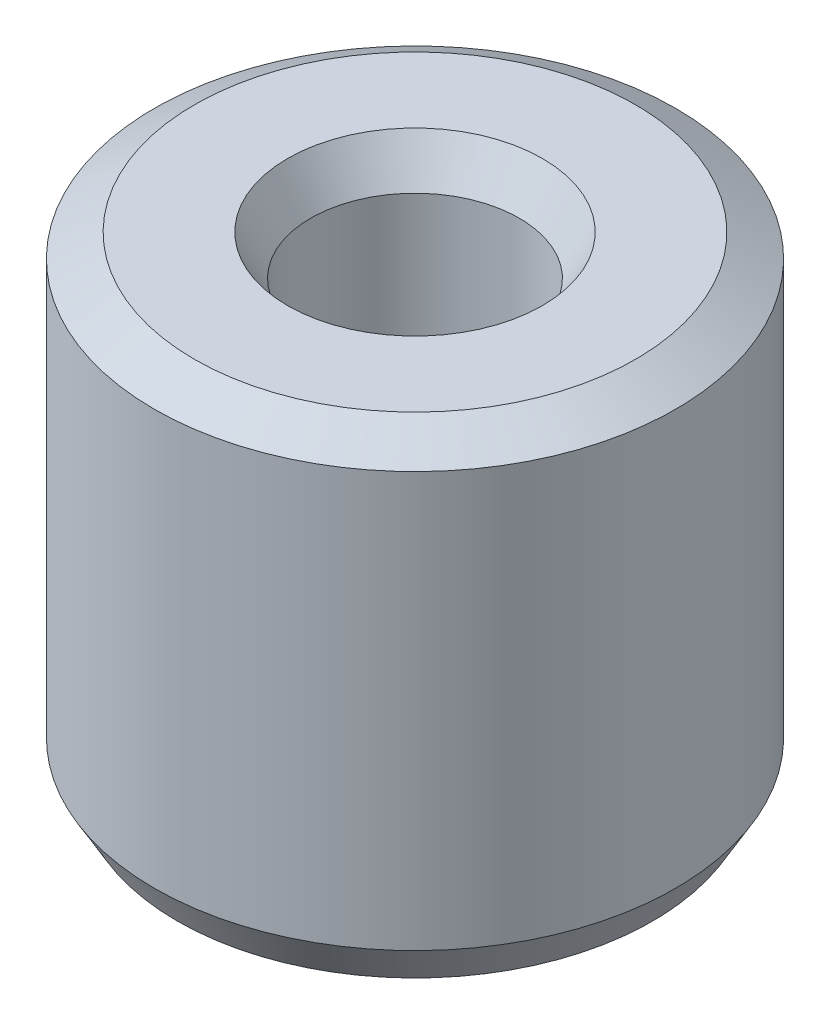
SolidWorks part; units mm, degrees
ref_plane "Front Plane" through (0, 0, 0) normal (0, 0, 1) x (1, 0, 0)
ref_plane "Top Plane" through (0, 0, 0) normal (0, 1, 0) x (1, 0, 0)
ref_plane "Right Plane" through (0, 0, 0) normal (1, 0, 0) x (0, 0, -1)
sketch "Sketch1" plane through (0, 0, 0) normal (0, 1, 0) x (1, 0, 0)
  circle A0 centre (0, 0) radius 32.5
  dimension "SLEEVE_OD" = 65
extrude "Boss-Extrude1" add sketch "Sketch1" along normal blind 59.6158
sketch "Sketch2" plane through (0, 0, 0) normal (0, 1, 0) x (1, 0, 0)
  circle A0 centre (0, 0) radius 13.0048
  dimension "BORE_D" = 26.0097
extrude "Cut-Extrude1" cut sketch "Sketch2" along normal through all
chamfer "Chamfer1" distance 2.887 angle 60 4 edges at (0, 59.6158, 13.0048) (0, 0, 13.0048) (0, 0, 32.5) (0, 59.6158, 32.5) first distance on face at (0, 59.6158, 13.0048) first distance on face at (0, 0, 13.0048) first distance on face at (0, 59.6158, 32.5)
